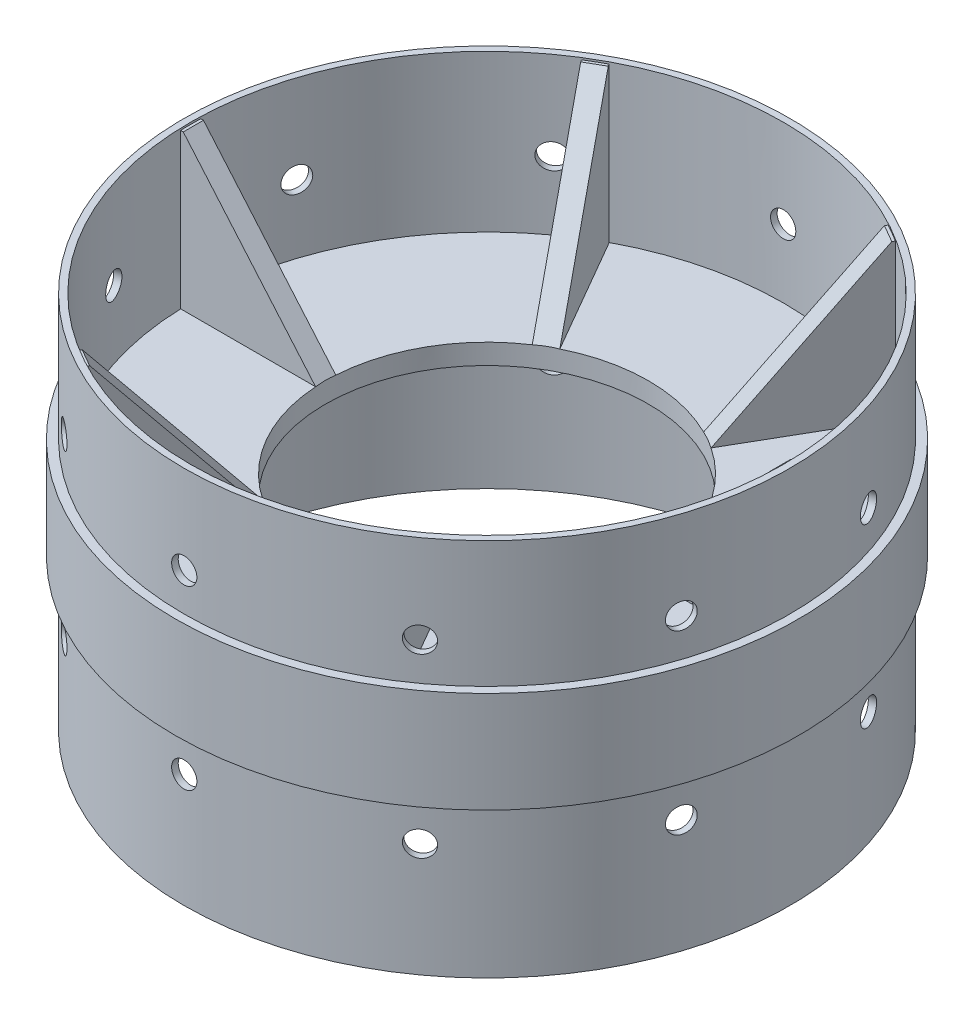
SolidWorks part; units mm, degrees
material "2024-T4"
ref_plane "Front Plane" through (0, 0, 0) normal (0, 0, 1) x (1, 0, 0)
ref_plane "Top Plane" through (0, 0, 0) normal (0, 1, 0) x (1, 0, 0)
ref_plane "Right Plane" through (0, 0, 0) normal (1, 0, 0) x (0, 0, -1)
sketch "Sketch1" plane through (0, 0, 0) normal (0, 1, 0) x (1, 0, 0)
  circle A0 centre (0, 0) radius 74.549
  circle A1 centre (0, 0) radius 78.359
  dimension "D1" = 149.098
  dimension "D2" = 156.718
extrude "Boss-Extrude1" add sketch "Sketch1" along normal blind 25.4
sketch "Sketch2" plane through (0, 25.4, 0) normal (0, 1, 0) x (1, 0, 0)
  circle A0 centre (0, 0) radius 76.2
  circle A1 centre (0, 0) radius 74.549
extrude "Boss-Extrude2" add sketch "Sketch2" along normal blind 31.75
sketch "Sketch3" plane through (0, 0, 0) normal (0, -1, 0) x (1, 0, 0)
  circle A0 centre (0, 0) radius 76.2
  circle A1 centre (0, 0) radius 74.549
  dimension "D1" = 152.4
extrude "Boss-Extrude3" add sketch "Sketch3" along normal blind 38.1
ref_plane "Plane1" through (0, 12.7, 0) normal (0, 1, 0) x (1, 0, 0)
sketch "Sketch4" plane through (0, 12.7, 0) normal (0, 1, 0) x (1, 0, 0)
  circle A0 centre (0, 0) radius 74.549
  circle A1 centre (0, 0) radius 40.64
  dimension "D1" = 81.28
extrude "Boss-Extrude4" add sketch "Sketch4" along normal blind 5.08
sketch "Sketch5" plane through (0, 17.78, 0) normal (0, 1, 0) x (1, 0, 0)
  line L0 (40.5605, 2.54) -> (74.5057, 2.54)
  line L2 (74.5057, -2.54) -> (40.5605, -2.54)
  line L3 (34.8136, 0) -> (44.1618, 0) construction
  line L19 (22.48, -33.8565) -> (39.4526, -63.2538)
  line L20 (35.0532, -65.7938) -> (18.0806, -36.3965)
  line L21 (-18.0806, -36.3965) -> (-35.0532, -65.7938)
  line L22 (-39.4526, -63.2538) -> (-22.48, -33.8565)
  line L29 (-40.5605, -2.54) -> (-74.5057, -2.54)
  line L30 (-74.5057, 2.54) -> (-40.5605, 2.54)
  line L31 (-22.48, 33.8565) -> (-39.4526, 63.2538)
  line L32 (-35.0532, 65.7938) -> (-18.0806, 36.3965)
  line L33 (18.0806, 36.3965) -> (35.0532, 65.7938)
  line L34 (39.4526, 63.2538) -> (22.48, 33.8565)
  circle A0 centre (0, 0) radius 40.64 construction
  arc A1 (39.4526, -63.2538) -> (35.0532, -65.7938) centre (0, 0) cw
  arc A2 (74.5057, 2.54) -> (74.5057, -2.54) centre (0, 0) cw
  circle A3 centre (0, 0) radius 74.549 construction
  arc A4 (40.5605, 2.54) -> (40.5605, -2.54) centre (0, 0) cw
  arc A19 (22.48, -33.8565) -> (18.0806, -36.3965) centre (0, 0) cw
  arc A20 (-35.0532, -65.7938) -> (-39.4526, -63.2538) centre (0, 0) cw
  arc A21 (-18.0806, -36.3965) -> (-22.48, -33.8565) centre (0, 0) cw
  arc A28 (-74.5057, -2.54) -> (-74.5057, 2.54) centre (0, 0) cw
  arc A29 (-40.5605, -2.54) -> (-40.5605, 2.54) centre (0, 0) cw
  arc A30 (-39.4526, 63.2538) -> (-35.0532, 65.7938) centre (0, 0) cw
  arc A31 (-22.48, 33.8565) -> (-18.0806, 36.3965) centre (0, 0) cw
  arc A32 (35.0532, 65.7938) -> (39.4526, 63.2538) centre (0, 0) cw
  arc A33 (18.0806, 36.3965) -> (22.48, 33.8565) centre (0, 0) cw
  point P34 (0, 0)
  point P40 (0, 0)
  dimension "D4" = 0
  dimension "D1" = 2.54
  dimension "D2" = 2.54
  dimension "D3" = 6
extrude "Boss-Extrude10" add sketch "Sketch5" along normal blind 38.862
sketch "Sketch6" plane through (0, 0, 2.54) normal (0, 0, 1) x (1, 0, 0)
  line L0 (74.2828, 57.15) -> (40.5605, 17.78)
  line L1 (40.5605, 17.78) -> (40.5605, 57.15)
  line L2 (40.5605, 57.15) -> (74.2828, 57.15)
  line L5 (76.2, 57.15) -> (-76.2, 57.15) construction
  point P6 (0, 0)
  point P7 (74.2828, 57.15)
extrude "Cut-Extrude1" cut sketch "Sketch6" against normal blind 5.08
pattern_circular "CirPattern1" count 6 over 360 about axis through (0, 12.7, 0) along (0, 1, 0) of "Cut-Extrude1"
sketch "Sketch7" plane through (0, 0, 0) normal (0, 0, 1) x (1, 0, 0)
  line L0 (0, 42.3302) -> (0, 74.728) construction
  line L1 (78.359, 25.4) -> (-78.359, 25.4) construction
  line L2 (-78.359, 12.7) -> (83.2334, 12.7) construction
  line L3 (-78.359, 25.4) -> (-78.359, 0) construction
  circle A0 centre (0, 34.925) radius 3.175
  circle A1 centre (0, -9.525) radius 3.175
  dimension "D1" = 6.35
  dimension "D2" = 9.525
extrude "Cut-Extrude2" cut sketch "Sketch7" against normal through all
ref_axis "Axis1" through (0, 42.3302, 0) along (0, 1, 0)
pattern_circular "CirPattern2" count 10 over 360 about axis through (0, 42.3302, 0) along (0, 1, 0) of "Cut-Extrude2"
